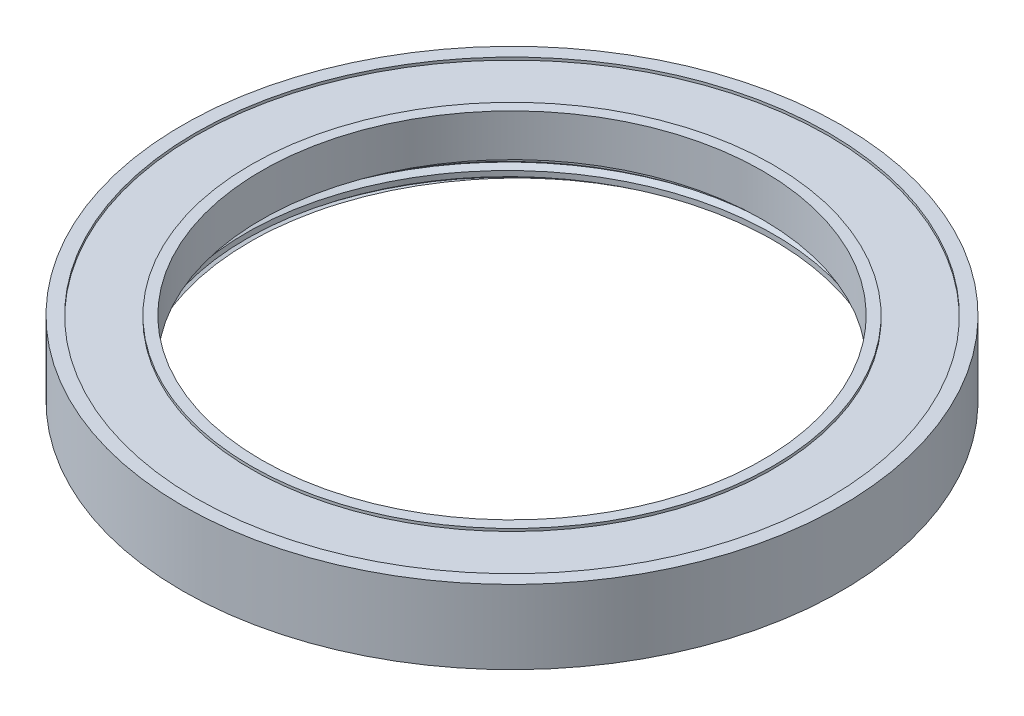
SolidWorks part; units mm, degrees
ref_plane "Front Plane" through (0, 0, 0) normal (0, 0, 1) x (1, 0, 0)
ref_plane "Top Plane" through (0, 0, 0) normal (0, 1, 0) x (1, 0, 0)
ref_plane "Right Plane" through (0, 0, 0) normal (1, 0, 0) x (0, 0, -1)
sketch "Sketch1" plane through (0, 0, 0) normal (1, 0, 0) x (0, 0, -1)
  line L0 (0, 0) -> (0, 62.5288) construction
  line L1 (47.5, 120) -> (47.5, 0)
  line L2 (47.5, 0) -> (62.5, 0)
  line L3 (62.5, 0) -> (62.5, 120)
  line L4 (62.5, 120) -> (47.5, 120)
  line L5 (47.5, 20.15) -> (62.5, 20.15)
  line L6 (62.5, 20.15) -> (62.5, 6.15)
  line L7 (62.5, 6.15) -> (47.5, 6.15)
  line L8 (47.5, 26.3) -> (62.5, 26.3)
  line L9 (47.5, 40.3) -> (62.5, 40.3)
  line L10 (47.5, 46.45) -> (62.5, 46.45)
  line L11 (47.5, 60.45) -> (62.5, 60.45)
  line L12 (47.5, 66.6) -> (62.5, 66.6)
  line L13 (49.5, 120) -> (49.5, 0)
  dimension "D1" = 15
  dimension "D2" = 120
  dimension "D3" = 14
  dimension "D4" = 6.15
  dimension "D5" = 6.15
  dimension "D6" = 14
  dimension "D7" = 6.15
  dimension "D8" = 14
  dimension "D9" = 6.15
  dimension "D10" = 13
  dimension "D11" = 62.5
sketch "Sketch2" plane through (0, 0, 0) normal (1, 0, 0) x (0, 0, -1)
  line L0 (0, 0) -> (0, 62.5288) construction
  line L1 (0, 0) -> (0, 62.5288) construction
  line L2 (47.5, 36.15) -> (47.5, 20.15)
  line L3 (47.5, 20.15) -> (62.5, 20.15)
  line L4 (62.5, 20.15) -> (62.5, 6.15)
  line L5 (62.5, 6.15) -> (47.5, 6.15)
  line L6 (47.5, 6.15) -> (47.5, 20.15)
  line L7 (47.5, 13.15) -> (62.5, 13.15) construction
  line L10 (49.5, 6.65) -> (60, 6.65)
  line L11 (47.5, 36.15) -> (49.5, 36.15)
  line L12 (49.5, 36.15) -> (49.5, 20.15)
  line L13 (49.5, -9.85) -> (60, -9.85)
  line L14 (47.5, 6.15) -> (50, 6.15)
  line L15 (47.5, 6.15) -> (47.5, 12.15)
  line L16 (47.5, 12.15) -> (50, 12.15)
  line L17 (50, 6.15) -> (50, 12.15)
  line L18 (49.5, 36.15) -> (60, 36.15)
  line L19 (49.5, 36.15) -> (49.5, 19.65)
  line L20 (49.5, 19.65) -> (60, 19.65)
  line L21 (60, 36.15) -> (60, 19.65)
  line L22 (49.5, -9.85) -> (49.5, 6.15)
  line L23 (60, -9.85) -> (60, 6.65)
  dimension "D1" = 16
  dimension "D2" = 6
  dimension "D3" = 10.5
  dimension "D4" = 0.5
  dimension "D5" = 60
revolve "Revolve1" add sketch "Sketch2" angle 360 about L1
thread "Thread1" pitch 2 start angle 0, offset 0, length 6, pitch 2.5, diameter 100
ref_plane "Plane1" through (50, 6.65, 0) normal (0, 0, -1) x (1, 0, 0)
sketch "Thread Profile1" plane through (50, 6.65, 0) normal (0, 0, -1) x (1, 0, 0)
  line L0 (0, 0) -> (0, 2) construction
  line L1 (0, 0) -> (1.0825, 0.625)
  line L2 (1.0825, 0.625) -> (1.0825, 0.875)
  line L3 (1.0825, 0.875) -> (0, 1.5)
  line L4 (1.0825, 0.75) -> (0, 0.75) construction
  line L11 (0, 0) -> (0, 1.5)
  point P2 (0, 0)
  dimension "Pitch" = 2
  dimension "Profile_Angle" = 60
  dimension "Profile_Land" = 0.25
  dimension "Profile_Height" = 1.0825
thread "Thread2" pitch 2 profile "Thread Profile2" start angle 0, offset 0, length 4, pitch 2.5, diameter 99
ref_plane "Plane2" through (-49.5, 36.15, 0) normal (0, 0, 1) x (-1, 0, 0)
sketch "Thread Profile2" plane through (-49.5, 36.15, 0) normal (0, 0, 1) x (-1, 0, 0)
  line L0 (0, 0) -> (0, 2) construction
  line L1 (0, 0) -> (1.0825, 0.625)
  line L2 (1.0825, 0.625) -> (1.0825, 0.875)
  line L3 (1.0825, 0.875) -> (0, 1.5)
  line L4 (1.0825, 0.75) -> (0, 0.75) construction
  line L11 (0, 0) -> (0, 1.5)
  point P2 (0, 0)
  dimension "Pitch" = 2
  dimension "Profile_Angle" = 60
  dimension "Profile_Land" = 0.25
  dimension "Profile_Height" = 1.0825
sketch "Sketch3" plane through (0, 0, 0) normal (0, 0, 1) x (1, 0, 0)
  line L0 (49.5, 19.65) -> (-49.5, 19.65) construction
  line L1 (47.5, 36.15) -> (-47.5, 36.15) construction
  line L2 (49.5, 19.65) -> (-49.5, 19.65)
  line L3 (47.5, 36.15) -> (-47.5, 36.15)
  line L4 (0, 19.65) -> (0, 31.525) construction
  line L6 (7.5, 20.5875) -> (-7.5, 20.5875)
  line L7 (7.5, 20.5875) -> (7.5, 30.5875)
  line L8 (7.5, 30.5875) -> (-7.5, 30.5875)
  line L9 (-7.5, 20.5875) -> (-7.5, 30.5875)
  line L10 (7.5, 20.5875) -> (-7.5, 30.5875) construction
  line L11 (7.5, 30.5875) -> (-7.5, 20.5875) construction
  spline S0 degree 2 poles (39.7724, 34.6536) (-6259.3756, 116.6344) (-40.0463, 34.4) (-30.5927, 34.275) (-15.2963, 34.15) (0, 34.025) (15.2963, 33.9) (30.5927, 33.775) (40.0463, 33.65) (49.5, 33.525) (49.5, 33.4) (49.5, 33.275) (40.0463, 33.15) (30.5927, 33.025) (15.2963, 32.9) (0, 32.775) (-15.2963, 32.65) (-30.5927, 32.525) (-40.0463, 32.4) (-49.5, 32.275) (-49.5, 32.15) (-49.5, 32.025) (-40.0463, 31.9) (-30.5927, 31.775) (-15.2963, 31.65) (0, 31.525) (15.2963, 31.4) (30.5927, 31.275) (40.0463, 31.15) (49.5, 31.025) (49.5, 30.9) (49.5, 1.371) (-49.4832, 30.64) knots -0.942277 -0.942277 -0.942277 0.05 0.05 0.1 0.1 0.15 0.15 0.2 0.2 0.25 0.25 0.3 0.3 0.35 0.35 0.4 0.4 0.45 0.45 0.5 0.5 0.55 0.55 0.6 0.6 0.65 0.65 0.7 0.7 0.75 0.75 1.693941 1.693941 1.693941 weights 37.609752 0.02869 1 0.951057 1 0.951057 1 0.951057 1 0.951057 1 0.951057 1 0.951057 1 0.951057 1 0.951057 1 0.951057 1 0.951057 1 0.951057 1 0.951057 1 0.951057 1 0.951057 1 0.076005 34.039872 only from (-49.5, 34.65) to (40.0463, 30.65) construction
  spline S1 degree 2 poles (-49.5, 34.65) (-49.5, 34.525) (-40.0463, 34.4) (-30.5927, 34.275) (-15.2963, 34.15) (0, 34.025) (15.2963, 33.9) (30.5927, 33.775) (40.0463, 33.65) (49.5, 33.525) (49.5, 33.4) (49.5, 33.275) (40.0463, 33.15) (30.5927, 33.025) (15.2963, 32.9) (0, 32.775) (-15.2963, 32.65) (-30.5927, 32.525) (-40.0463, 32.4) (-49.5, 32.275) (-49.5, 32.15) (-49.5, 32.025) (-40.0463, 31.9) (-30.5927, 31.775) (-15.2963, 31.65) (0, 31.525) (15.2963, 31.4) (30.5927, 31.275) (40.0463, 31.15) (49.5, 31.025) (49.5, 30.9) (49.5, 30.775) (40.0463, 30.65) knots 0 0 0 0.05 0.05 0.1 0.1 0.15 0.15 0.2 0.2 0.25 0.25 0.3 0.3 0.35 0.35 0.4 0.4 0.45 0.45 0.5 0.5 0.55 0.55 0.6 0.6 0.65 0.65 0.7 0.7 0.75 0.75 0.8 0.8 0.8 weights 1 0.951057 1 0.951057 1 0.951057 1 0.951057 1 0.951057 1 0.951057 1 0.951057 1 0.951057 1 0.951057 1 0.951057 1 0.951057 1 0.951057 1 0.951057 1 0.951057 1 0.951057 1 0.951057 1
  point P9 (0, 25.5875)
  dimension "D1" = 15
  dimension "D2" = 10
extrude "Cut-Extrude1" cut sketch "Sketch3" against normal through all contours L9 L6 L7 L8
sketch "Sketch4" plane through (0, 0, 0) normal (1, 0, 0) x (0, 0, -1)
  line L0 (62.5, 20.15) -> (-62.5, 20.15) construction
  line L1 (62.5, 20.15) -> (-62.5, 20.15)
  line L2 (-62.5, 6.15) -> (62.5, 6.15) construction
  line L3 (-62.5, 20.15) -> (62.5, 20.15)
  line L4 (-62.5, 20.15) -> (-62.5, 40.1698)
  line L5 (-62.5, 40.1698) -> (62.5, 40.1698)
  line L6 (62.5, 20.15) -> (62.5, 40.1698)
  line L7 (-62.5, 20.15) -> (62.5, 20.15)
  line L8 (-62.5, 20.15) -> (-62.5, 6.15)
  line L9 (-62.5, 6.15) -> (62.5, 6.15)
  line L10 (62.5, 20.15) -> (62.5, 6.15)
extrude "Cut-Extrude2" cut sketch "Sketch4" against normal through all both and the other way through all contours L1 L6 L5 L4
